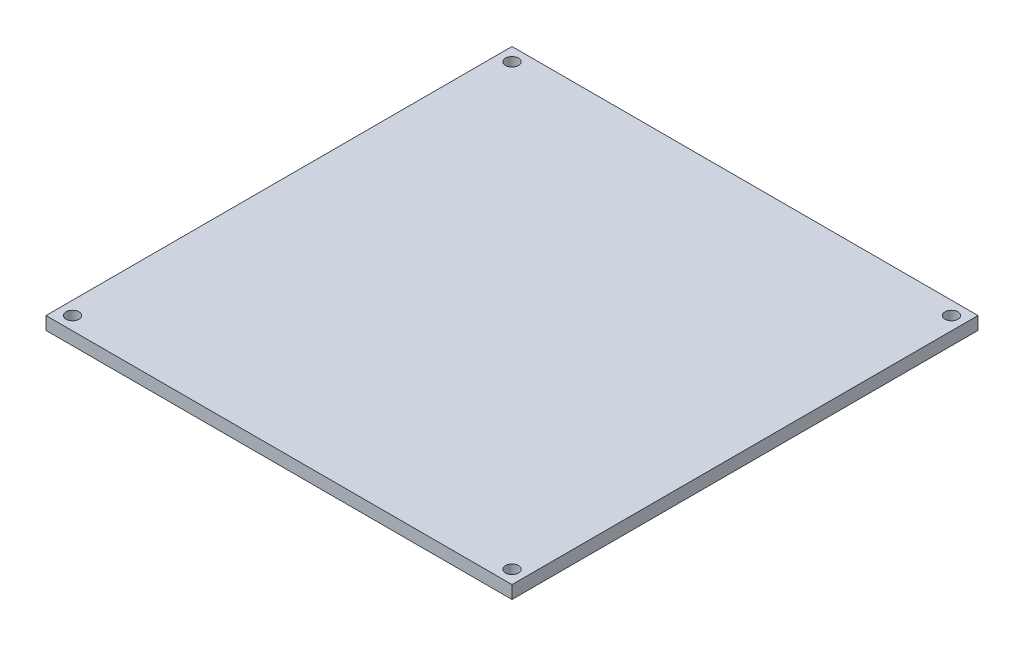
SolidWorks part; units mm, degrees
ref_plane "Front Plane" through (0, 0, 0) normal (0, 0, 1) x (1, 0, 0)
ref_plane "Top Plane" through (0, 0, 0) normal (0, 1, 0) x (1, 0, 0)
ref_plane "Right Plane" through (0, 0, 0) normal (1, 0, 0) x (0, 0, -1)
sketch "Sketch1" plane through (0, 0, 0) normal (0, 1, 0) x (1, 0, 0)
  line L2 (0, -18.4837) -> (0, -26.4272) construction
  line L3 (-36, 53.5163) -> (-36, -18.4837)
  line L4 (-36, 53.5163) -> (36, 53.5163)
  line L6 (-36, -18.4837) -> (36, -18.4837)
  line L7 (36, 53.5163) -> (36, -18.4837)
  line L13 (-34.6565, 52.1728) -> (-33.2423, 50.7585) construction
  circle A2 centre (-33.9494, 51.4657) radius 1
  circle A3 centre (33.9494, 51.4657) radius 1
  circle A4 centre (33.9494, -16.4331) radius 1
  circle A5 centre (-33.9494, -16.4331) radius 1
  dimension "D1" = 72
  dimension "D2" = 36
extrude "Boss-Extrude1" add sketch "Sketch1" along normal blind 2
